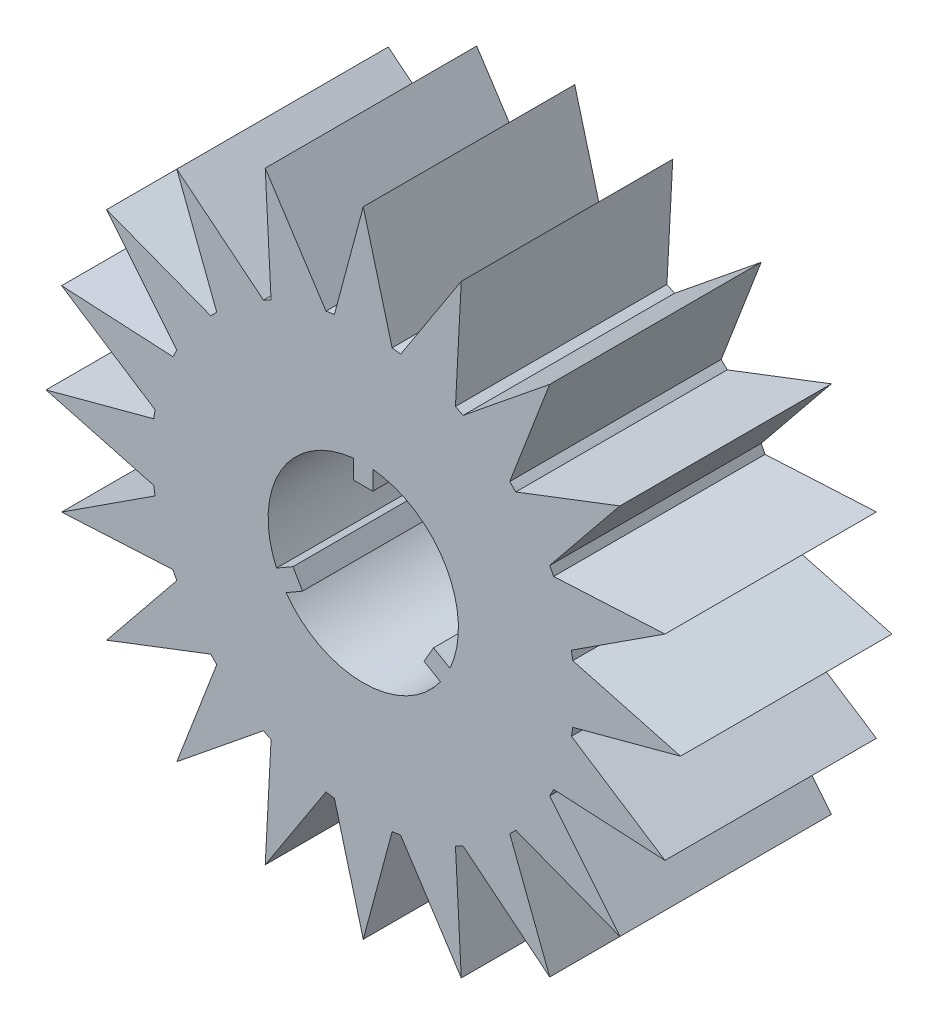
SolidWorks part; units mm, degrees
ref_plane "Front Plane" through (0, 0, 0) normal (0, 0, 1) x (1, 0, 0)
ref_plane "Top Plane" through (0, 0, 0) normal (0, 1, 0) x (1, 0, 0)
ref_plane "Right Plane" through (0, 0, 0) normal (1, 0, 0) x (0, 0, -1)
sketch "Sketch1" plane through (0, 0, 0) normal (0, 0, 1) x (1, 0, 0)
  line L0 (0, 15) -> (-1.3648, 9.9064)
  line L1 (0, 15) -> (1.3648, 9.9064)
  line L2 (4.6353, 14.2658) -> (4.3593, 8.9998)
  line L3 (4.6353, 14.2658) -> (1.7632, 9.8433)
  line L4 (8.8168, 12.1353) -> (6.927, 7.2122)
  line L5 (8.8168, 12.1353) -> (4.7187, 8.8167)
  line L6 (12.1353, 8.8168) -> (8.8167, 4.7187)
  line L7 (12.1353, 8.8168) -> (7.2122, 6.927)
  line L8 (14.2658, 4.6353) -> (9.8433, 1.7632)
  line L9 (14.2658, 4.6353) -> (8.9998, 4.3593)
  line L10 (15, 0) -> (9.9064, -1.3648)
  line L11 (15, 0) -> (9.9064, 1.3648)
  line L12 (14.2658, -4.6353) -> (8.9998, -4.3593)
  line L13 (14.2658, -4.6353) -> (9.8433, -1.7632)
  line L14 (12.1353, -8.8168) -> (7.2122, -6.927)
  line L15 (12.1353, -8.8168) -> (8.8167, -4.7187)
  line L16 (8.8168, -12.1353) -> (4.7187, -8.8167)
  line L17 (8.8168, -12.1353) -> (6.927, -7.2122)
  line L18 (4.6353, -14.2658) -> (1.7632, -9.8433)
  line L19 (4.6353, -14.2658) -> (4.3593, -8.9998)
  line L20 (0, -15) -> (-1.3648, -9.9064)
  line L21 (0, -15) -> (1.3648, -9.9064)
  line L22 (-4.6353, -14.2658) -> (-4.3593, -8.9998)
  line L23 (-4.6353, -14.2658) -> (-1.7632, -9.8433)
  line L24 (-8.8168, -12.1353) -> (-6.927, -7.2122)
  line L25 (-8.8168, -12.1353) -> (-4.7187, -8.8167)
  line L26 (-12.1353, -8.8168) -> (-8.8167, -4.7187)
  line L27 (-12.1353, -8.8168) -> (-7.2122, -6.927)
  line L28 (-14.2658, -4.6353) -> (-9.8433, -1.7632)
  line L29 (-14.2658, -4.6353) -> (-8.9998, -4.3593)
  line L30 (-15, 0) -> (-9.9064, 1.3648)
  line L31 (-15, 0) -> (-9.9064, -1.3648)
  line L32 (-14.2658, 4.6353) -> (-8.9998, 4.3593)
  line L33 (-14.2658, 4.6353) -> (-9.8433, 1.7632)
  line L34 (-12.1353, 8.8168) -> (-7.2122, 6.927)
  line L35 (-12.1353, 8.8168) -> (-8.8167, 4.7187)
  line L36 (-8.8168, 12.1353) -> (-4.7187, 8.8167)
  line L37 (-8.8168, 12.1353) -> (-6.927, 7.2122)
  line L38 (-4.6353, 14.2658) -> (-1.7632, 9.8433)
  line L39 (-4.6353, 14.2658) -> (-4.3593, 8.9998)
  line L40 (0.45, 3.5774) -> (-0.45, 3.5774)
  line L41 (-0.45, 3.5774) -> (-0.45, 4.4774)
  line L42 (0.45, 3.5774) -> (0.45, 4.4774)
  line L43 (2.8732, -2.1784) -> (3.6526, -2.6284)
  line L44 (2.8732, -2.1784) -> (3.3232, -1.399)
  line L45 (3.3232, -1.399) -> (4.1026, -1.849)
  line L46 (-3.3232, -1.399) -> (-4.1026, -1.849)
  line L47 (-3.3232, -1.399) -> (-2.8732, -2.1784)
  line L48 (-2.8732, -2.1784) -> (-3.6526, -2.6284)
  arc A0 (-1.7632, -9.8433) -> (-1.3648, -9.9064) centre (0, 0) ccw
  arc A1 (-0.45, 4.4774) -> (-4.1026, -1.849) centre (0, 0) ccw
  arc A4 (-4.7187, -8.8167) -> (-4.3593, -8.9998) centre (0, 0) ccw
  arc A5 (-7.2122, -6.927) -> (-6.927, -7.2122) centre (0, 0) ccw
  arc A6 (-8.9998, -4.3593) -> (-8.8167, -4.7187) centre (0, 0) ccw
  arc A7 (-9.9064, -1.3648) -> (-9.8433, -1.7632) centre (0, 0) ccw
  arc A8 (-9.8433, 1.7632) -> (-9.9064, 1.3648) centre (0, 0) ccw
  arc A9 (-8.8167, 4.7187) -> (-8.9998, 4.3593) centre (0, 0) ccw
  arc A10 (-6.927, 7.2122) -> (-7.2122, 6.927) centre (0, 0) ccw
  arc A11 (-4.3593, 8.9998) -> (-4.7187, 8.8167) centre (0, 0) ccw
  arc A12 (-1.3648, 9.9064) -> (-1.7632, 9.8433) centre (0, 0) ccw
  arc A13 (1.7632, 9.8433) -> (1.3648, 9.9064) centre (0, 0) ccw
  arc A14 (4.7187, 8.8167) -> (4.3593, 8.9998) centre (0, 0) ccw
  arc A15 (7.2122, 6.927) -> (6.927, 7.2122) centre (0, 0) ccw
  arc A16 (8.9998, 4.3593) -> (8.8167, 4.7187) centre (0, 0) ccw
  arc A17 (9.9064, 1.3648) -> (9.8433, 1.7632) centre (0, 0) ccw
  arc A18 (9.8433, -1.7632) -> (9.9064, -1.3648) centre (0, 0) ccw
  arc A19 (8.8167, -4.7187) -> (8.9998, -4.3593) centre (0, 0) ccw
  arc A20 (6.927, -7.2122) -> (7.2122, -6.927) centre (0, 0) ccw
  arc A21 (4.3593, -8.9998) -> (4.7187, -8.8167) centre (0, 0) ccw
  arc A22 (1.3648, -9.9064) -> (1.7632, -9.8433) centre (0, 0) ccw
  arc A26 (4.1026, -1.849) -> (0.45, 4.4774) centre (0, 0) ccw
  arc A27 (-3.6526, -2.6284) -> (3.6526, -2.6284) centre (0, 0) ccw
  point P9 (0, 3.5774)
  point P69 (0, 0)
  point P81 (0, 0)
  dimension "D2" = 20
  dimension "D3" = 9
  dimension "D4" = 30
  dimension "D1" = 30
  dimension "D6" = 0.9
  dimension "D7" = 0.9
  dimension "D5" = 20
  dimension "D8" = 3
extrude "Boss-Extrude1" add sketch "Sketch1" along normal blind 10 contours L21 A22 L18 L19 A21 L16 L17 A20 L14 L15 A19 L12 L13 A18 L10 L11 A17 L8 L9 A16 L6 L7 A15 L4 L5 A14 L2 L3 A13 L1 L0 A12 L38 L39 A11 L36 L37 A10 L34 L35 A9 L32 L33 A8 L30 L31 A7 L28 L29 A6 L26 region at (0.2726, 12.3434, 0)
equation "\"Outer Tooth Diameter\" = 30mm"
equation "\"Outer Body Diameter\"= \"Outer Tooth Diameter\" - 10mm"
equation "\"Inner Body Diameter\"= 9mm"
equation "\"Slot Extrude Length\"= 0.9mm"
equation "\"D2@Sketch1\"=\"Outer Body Diameter\""
equation "\"D3@Sketch1\"=\"Inner Body Diameter\""
equation "\"D1@Sketch1\"=\"Outer Tooth Diameter\""
equation "\"D6@Sketch1\"=\"Slot Extrude Length\""
equation "\"Slot Extrude Width\"= 0.9mm"
equation "\"D7@Sketch1\"=\"Slot Extrude Width\""
equation "\"Gear Thickness\"= 10mm"
equation "\"D1@Boss-Extrude1\"=\"Gear Thickness\""
